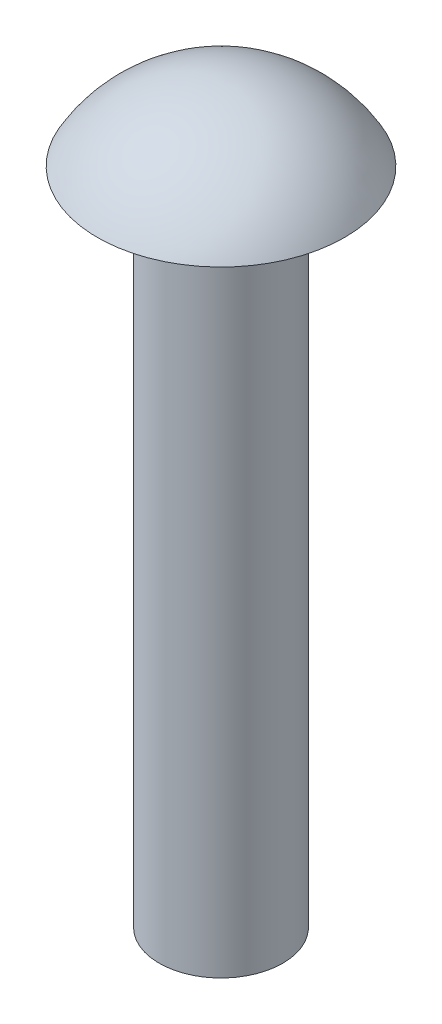
SolidWorks part; units mm, degrees
material "AISI 1020 Steel, Cold Rolled"
ref_plane "前视基准面" through (0, 0, 0) normal (0, 0, 1) x (1, 0, 0)
ref_plane "上视基准面" through (0, 0, 0) normal (0, 1, 0) x (1, 0, 0)
ref_plane "右视基准面" through (0, 0, 0) normal (1, 0, 0) x (0, 0, -1)
sketch "Sketch1" plane through (0, 0, 0) normal (0, 0, 1) x (1, 0, 0)
  line L0 (0, 0) -> (0, 1.75)
  line L1 (0, 0) -> (3, 0)
  line L2 (0, -1000) -> (0, 49000) construction
  arc A0 (0, 1.75) -> (3, 0) centre (0, -1.6964) cw
  dimension "D1" = 1.75
  dimension "D2" = 3
  dimension "D3" = 0
revolve "Revolve1" add sketch "Sketch1" angle 360 about L2
sketch "Sketch2" plane through (0, 0, 0) normal (0, -1, 0) x (1, 0, 0)
  circle A0 centre (0, 0) radius 1.5
  dimension "D1" = 3
extrude "Boss-Extrude1" add sketch "Sketch2" along normal blind 16
